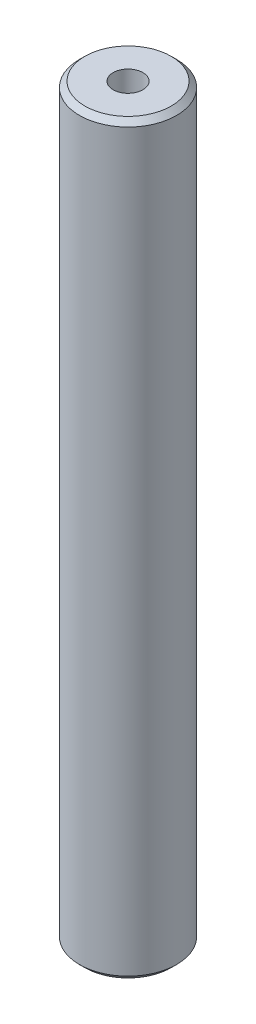
SolidWorks part; units mm, degrees
ref_plane "Front Plane" through (0, 0, 0) normal (0, 0, 1) x (1, 0, 0)
ref_plane "Top Plane" through (0, 0, 0) normal (0, 1, 0) x (1, 0, 0)
ref_plane "Right Plane" through (0, 0, 0) normal (1, 0, 0) x (0, 0, -1)
sketch "Sketch1" plane through (0, 0, 0) normal (0, 1, 0) x (1, 0, 0)
  circle A0 centre (0, 0) radius 15
  dimension "SHAFT_OD" = 30
extrude "Boss-Extrude1" add sketch "Sketch1" along normal blind 230.4613
sketch "Sketch2" plane through (0, 0, 0) normal (0, 1, 0) x (1, 0, 0)
  circle A0 centre (0, 0) radius 4.5993
  dimension "BORE_D" = 9.1985
extrude "Cut-Extrude1" cut sketch "Sketch2" along normal through all
chamfer "Chamfer1" distance 1.672 angle 45 2 edges at (0, 230.4613, 15) (0, 0, 15)
